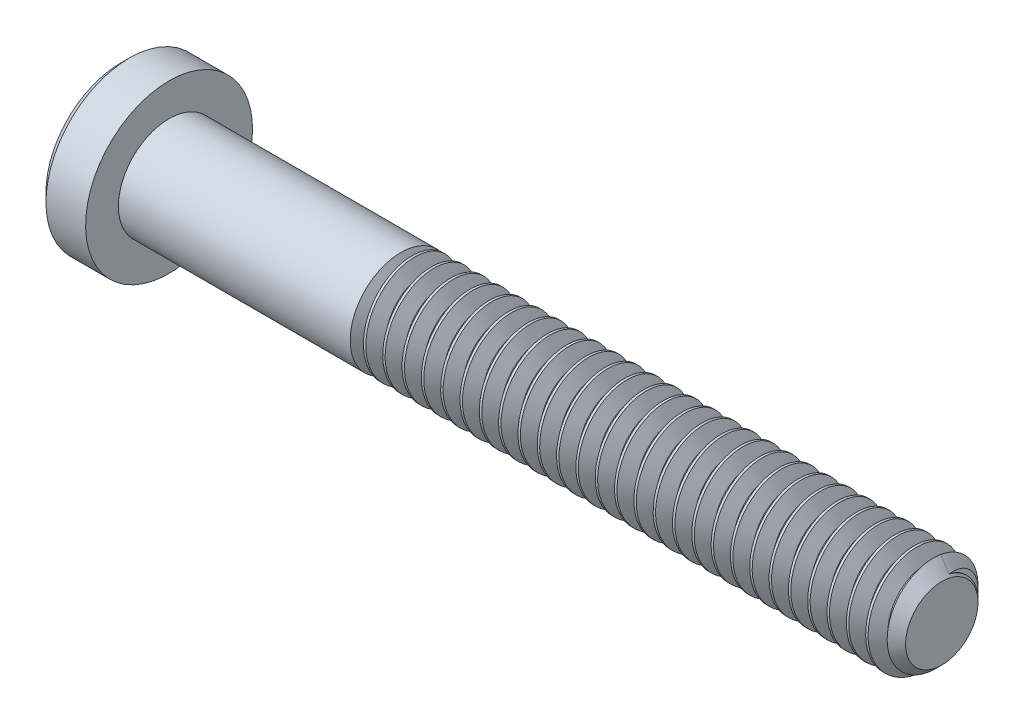
SolidWorks part; units mm, degrees
material "Alloy Steel"
ref_plane "Front Plane" through (0, 0, 0) normal (0, 0, 1) x (1, 0, 0)
ref_plane "Top Plane" through (0, 0, 0) normal (0, 1, 0) x (1, 0, 0)
ref_plane "Right Plane" through (0, 0, 0) normal (1, 0, 0) x (0, 0, -1)
sketch "Sketch1" plane through (0, 0, 0) normal (0, 0, 1) x (1, 0, 0)
  line L0 (15.875, 0) -> (-15.875, 0) construction
  line L1 (15.875, 2.0828) -> (15.875, -2.0828) construction
  line L2 (-15.875, 3.429) -> (-15.875, -3.429) construction
  line L3 (-15.875, 3.429) -> (-17.5038, 3.429) construction
  line L4 (-17.5038, 3.429) -> (-17.8594, 3.0734) construction
  line L5 (-17.8594, 3.0734) -> (-17.8594, -3.0734) construction
  line L6 (-17.8594, -3.0734) -> (-17.5038, -3.429) construction
  line L7 (-17.5038, -3.429) -> (-15.875, -3.429) construction
  line L8 (-6.35, 2.0828) -> (-6.35, -2.0828) construction
  point P7 (-16.3354, 0)
  point P12 (12.7, -2.0828)
  dimension "D1" = 45
  dimension "D2" = 3.175
  dimension "Dec." = 4.1656
  dimension "Length" = 31.75
  dimension "Head Dia" = 6.858
  dimension "Head Height" = 1.9844
  dimension "Hex Depth" = 1.524
  dimension "Chamfer" = 0.3556
  dimension "Thread Length" = 22.225
ref_plane "Plane1" through (15.875, 0, 0) normal (1, 0, 0) x (0, 0, -1)
ref_plane "Plane2" through (-17.8594, 0, 0) normal (1, 0, 0) x (0, 0, -1)
sketch "Sketch2" plane through (15.875, 0, 0) normal (1, 0, 0) x (0, 0, -1)
  circle A0 centre (0, 0) radius 2.0828
extrude "Boss-Extrude1" add sketch "Sketch2" against normal up to vertex (22.225 mm away) up to point (-6.35, 2.0828, 0)
sketch "Sketch3" plane through (15.875, 0, 0) normal (1, 0, 0) x (0, 0, -1)
  circle A0 centre (0, 0) radius 2.0828 construction
  circle A1 centre (0, 0) radius 2.0828
curve "Helix/Spiral1" pitch 0.7937 height 23.0188 turns 29 parameters "Pitch"=0.7937
chamfer "Chamfer1" distance 0.5953 angle 45 1 edges at (15.875, 0, -2.0828)
sketch "Sketch5" plane through (0, 0, 0) normal (0, 0, 1) x (1, 0, 0)
  line L0 (15.5277, 2.0828) -> (16.2223, 2.0828)
  line L1 (16.2223, 2.0828) -> (15.9246, 1.5672)
  line L2 (15.9246, 1.5672) -> (15.8254, 1.5672)
  line L3 (15.8254, 1.5672) -> (15.5277, 2.0828)
  line L4 (15.875, 1.5672) -> (15.875, 2.0828) construction
  line L5 (15.6766, 1.825) -> (16.0734, 1.825) construction
  dimension "D1" = 60
  dimension "D2" = 0.3969
  dimension "D3" = 0.0992
sweep "Cut-Sweep1" cut profiles "Sketch5" path "Helix/Spiral1"
sketch "Sketch4" plane through (-17.8594, 0, 0) normal (1, 0, 0) x (0, 0, -1)
  line L0 (-3.429, 0.7937) -> (3.429, 0.7937) construction
  line L1 (0, 1.1457) -> (-0.9922, 0.5728)
  line L2 (-0.9922, 0.5728) -> (-0.9922, -0.5728)
  line L3 (-0.9922, -0.5728) -> (0, -1.1457)
  line L4 (0, -1.1457) -> (0.9922, -0.5728)
  line L5 (0.9922, -0.5728) -> (0.9922, 0.5728)
  line L6 (0.9922, 0.5728) -> (0, 1.1457)
  line L7 (0, 0) -> (0, 0.7937) construction
  circle A0 centre (0, 0) radius 0.9922 construction
  dimension "D1" = 6.858
  dimension "Hex Size" = 1.9844
  dimension "D2" = 0.7937
sketch "Sketch9" plane through (0, 0, 0) normal (0, 0, 1) x (1, 0, 0)
  line L0 (-15.875, 0) -> (-15.875, 2.0828)
  line L1 (-15.875, 3.429) -> (-15.875, -3.429) construction
  line L2 (-15.875, 2.0828) -> (-6.35, 2.0828)
  line L3 (-6.35, 2.0828) -> (-5.1475, 0)
  line L4 (15.875, 0) -> (-15.875, 0) construction
  line L5 (-15.875, 0) -> (-5.1475, 0)
  dimension "D1" = 60
revolve "Revolve2" add sketch "Sketch9" angle 360 about L5
sketch "Sketch6" plane through (0, 0, 0) normal (0, 0, 1) x (1, 0, 0)
  line L0 (-17.5038, 3.429) -> (-17.8594, 3.0734) construction
  line L1 (-15.875, 3.429) -> (-17.5038, 3.429) construction
  line L2 (-15.875, 3.429) -> (-15.875, -3.429) construction
  line L3 (-17.8594, 3.0734) -> (-17.8594, -3.0734) construction
  line L4 (-17.5038, 3.429) -> (-17.8594, 3.0734)
  line L5 (-15.875, 3.429) -> (-17.5038, 3.429)
  line L6 (-15.875, 3.429) -> (-15.875, 0)
  line L7 (-17.8594, 3.0734) -> (-17.8594, 0)
  line L8 (-15.875, 0) -> (-17.8594, 0) construction
  line L9 (-15.875, 0) -> (-17.8594, 0)
revolve "Revolve1" add sketch "Sketch6" angle 360 about L8
extrude "Cut-Extrude1" cut sketch "Sketch4" along normal up to vertex (1.524 mm away) up to point (-16.3354, 0, 0)
sketch "Sketch8" plane through (-17.8594, 0, 0) normal (-1, 0, 0) x (0, 0, 1)
  circle A1 centre (0, 0) radius 1.1457
extrude "Cut-Extrude2" cut sketch "Sketch8" against normal through all draft 45
equation "\"D3@Helix/Spiral1\" = \"Thread Length@Sketch1\"+\"Pitch@Helix/Spiral1\""
equation "\"D3@Sketch5\" = \"Pitch@Helix/Spiral1\"*.125"
equation "\"D2@Sketch5\" = \"Pitch@Helix/Spiral1\"*.50"
equation "\"D1@Chamfer1\" = \"Pitch@Helix/Spiral1\"*.75"
equation "\"D2@Sketch1\" = \"Pitch@Helix/Spiral1\"*4"
equation "\"D1@Sketch4\" = \"Head Dia@Sketch1\""
